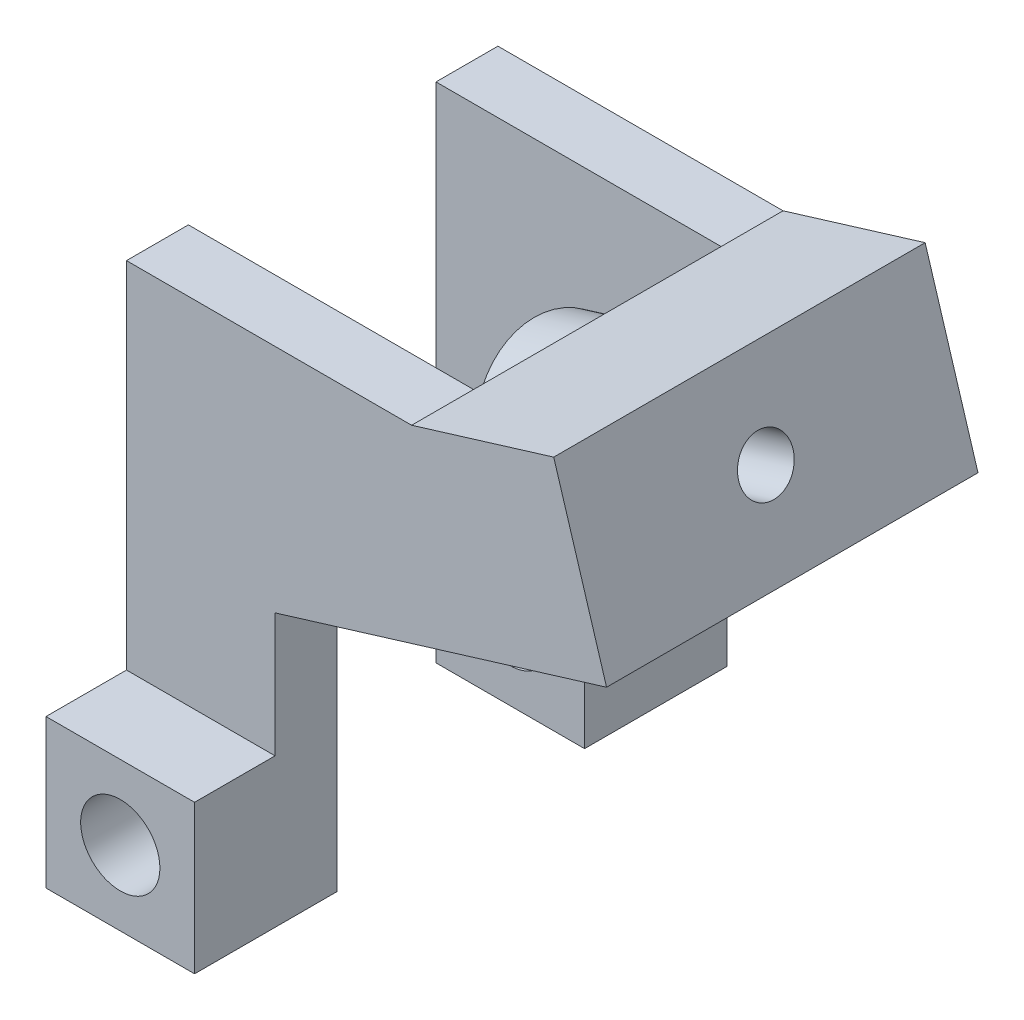
SolidWorks part; units mm, degrees
ref_plane "Front Plane" through (0, 0, 0) normal (0, 0, 1) x (1, 0, 0)
ref_plane "Top Plane" through (0, 0, 0) normal (0, 1, 0) x (1, 0, 0)
ref_plane "Right Plane" through (0, 0, 0) normal (1, 0, 0) x (0, 0, -1)
sketch "Sketch1" plane through (0, 0, 0) normal (0, 0, 1) x (1, 0, 0)
  line L0 (-3.5137, -7.6412) -> (4.1063, -7.6412)
  line L1 (4.1063, -7.6412) -> (4.1063, 6.3288)
  line L2 (4.1063, 6.3288) -> (13.8224, 9.2993)
  line L3 (4.1063, 6.3288) -> (20.8436, 6.3288) construction
  line L4 (13.8224, 9.2993) -> (11.1118, 18.1652)
  line L5 (11.1118, 18.1652) -> (-3.5137, 18.1652)
  line L6 (-3.5137, 18.1652) -> (-3.5137, -7.6412)
  dimension "D1" = 7.62
  dimension "D2" = 13.97
  dimension "D3" = 17
  dimension "D4" = 10.16
  dimension "D5" = 9.271
extrude "Boss-Extrude1" add sketch "Sketch1" along normal mid plane 19.05
sketch "Sketch2" plane through (0, 0, 0) normal (1, 0, 0) x (0, 0, -1)
  line L0 (0, 18.1652) -> (0, -7.6412) construction
  line L1 (-6.35, 18.1652) -> (6.35, 18.1652)
  line L2 (-6.35, 18.1652) -> (-6.35, -7.6412)
  line L3 (-6.35, -7.6412) -> (6.35, -7.6412)
  line L4 (6.35, 18.1652) -> (6.35, -7.6412)
  line L6 (-9.525, 18.1652) -> (9.525, 18.1652) construction
  line L7 (-9.525, -7.6412) -> (9.525, -7.6412) construction
  dimension "D1" = 12.7
extrude "Cut-Extrude1" cut sketch "Sketch2" against normal through all both and the other way through all
sketch "Sketch3" plane through (15.2409, 4.6596, 0) normal (0.9563, 0.2924, 0) x (0, 0, -1)
  line L0 (0, 14.1227) -> (0, 4.8517) construction
  line L1 (-9.525, 14.1227) -> (9.525, 14.1227)
  line L2 (-9.525, 14.1227) -> (-9.525, 4.8517)
  line L3 (-9.525, 4.8517) -> (9.525, 4.8517)
  line L4 (9.525, 14.1227) -> (9.525, 4.8517)
  circle A0 centre (0, 9.4872) radius 4.064
  circle A1 centre (0, 9.4872) radius 1.397
  line M4 (-9.525, 4.8517) -> (-6.35, 4.8517)
  line M5 (-6.35, 4.8517) -> (-6.35, 14.1227)
  line M6 (-6.35, 14.1227) -> (-9.525, 14.1227)
  line M7 (-9.525, 14.1227) -> (-9.525, 4.8517)
  dimension "D1" = 2.794
  dimension "D2" = 8.128
extrude "Boss-Extrude2" add sketch "Sketch3" along normal blind 7.62 contours M7 M4 M5 M6 | L1 L0 A0 L3 L4 | L0 L1 L3 A0 M5 | A0 L0 A1 | L0 A0 A1 region at (12.4671, 13.7323, -6.0262) region at (12.4671, 13.7323, 4.3176) region at (12.4671, 13.7323, -1.8765) region at (12.4671, 13.7323, 1.8765) region at (12.4671, 13.7323, 7.9375)
extrude "Boss-Extrude3" add sketch "Sketch3<3>" against normal blind 3.556 contours L0 A0 A1 | A0 L0 A1 region at (12.4671, 13.7323, -1.8765) region at (12.4671, 13.7323, 1.8765)
sketch "Sketch3<3>" plane through (15.2409, 4.6596, 0) normal (0.9563, 0.2924, 0) x (0, 0, -1) same geometry as "Sketch3"
sketch "Sketch4" plane through (4.1063, 0, 0) normal (1, 0, 0) x (0, 0, -1)
  line L1 (-13.6525, -0.0212) -> (-9.525, -0.0212)
  line L2 (-13.6525, -0.0212) -> (-13.6525, -7.6412)
  line L3 (-13.6525, -7.6412) -> (-9.525, -7.6412)
  line L4 (-9.525, -0.0212) -> (-9.525, -7.6412)
  dimension "D1" = 4.1275
  dimension "D2" = 7.62
extrude "Boss-Extrude4" add sketch "Sketch4" against normal up to surface (7.62 mm away) up to face at (-3.5137, 5.262, 7.9375)
sketch "Sketch5" plane through (0, 0, 13.6525) normal (0, 0, 1) x (1, 0, 0)
  line L0 (0.2963, -0.0212) -> (0.2963, -7.6412) construction
  line L1 (-3.5137, -0.0212) -> (4.1063, -0.0212) construction
  line L2 (-3.5137, -7.6412) -> (4.1063, -7.6412) construction
  circle A0 centre (0.2963, -3.8312) radius 2.032
  dimension "D1" = 4.064
extrude "Cut-Extrude2" cut sketch "Sketch5" against normal up to surface (7.3025 mm away) up to face at (4.3533, 6.1127, 6.35)
mirror "Mirror1" about plane through (0, 0, 0) normal (0, 0, 1) of "Boss-Extrude4", "Cut-Extrude2"
